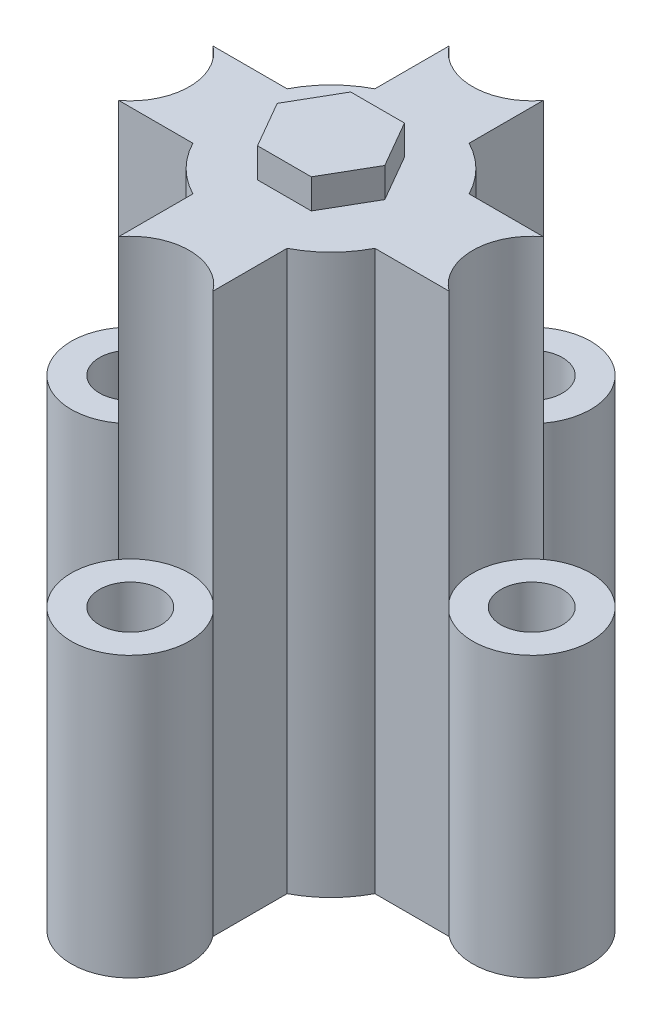
SolidWorks part; units mm, degrees
ref_plane "Front Plane" through (0, 0, 0) normal (0, 0, 1) x (1, 0, 0)
ref_plane "Top Plane" through (0, 0, 0) normal (0, 1, 0) x (1, 0, 0)
ref_plane "Right Plane" through (0, 0, 0) normal (1, 0, 0) x (0, 0, -1)
sketch "Sketch1" plane through (0, 0, 0) normal (0, 1, 0) x (1, 0, 0)
  line L1 (17.7275, 5.0583) -> (9.768, 5.0583)
  line L2 (17.7275, -5.0583) -> (9.768, -5.0583)
  line L3 (5.0583, -17.7275) -> (5.0583, -9.768)
  line L4 (-5.0583, -17.7275) -> (-5.0583, -9.768)
  line L5 (-17.7275, -5.0583) -> (-9.768, -5.0583)
  line L6 (-17.7275, 5.0583) -> (-9.768, 5.0583)
  line L7 (-5.0583, 17.7275) -> (-5.0583, 9.768)
  line L8 (5.0583, 17.7275) -> (5.0583, 9.768)
  circle A0 centre (0, 0) radius 11
  circle A4 centre (21.548, 0) radius 6.339
  circle A6 centre (0, -21.548) radius 6.339
  circle A8 centre (-21.548, 0) radius 6.339
  circle A10 centre (0, 21.548) radius 6.339
  circle A12 centre (21.548, 0) radius 3.302
  circle A13 centre (0, -21.548) radius 3.302
  circle A14 centre (-21.548, 0) radius 3.302
  circle A15 centre (0, 21.548) radius 3.302
  point P4 (13.7477, -5.0583)
  point P35 (0, 0)
  point P38 (0, 0)
  dimension "D1" = 21.548
  dimension "D2" = 12.678
  dimension "D3" = 6.604
  dimension "D5" = 22
  dimension "D4" = 7.9595
  dimension "D6" = 4
  dimension "D8" = 10.1166
  dimension "D9" = 7.9595
  dimension "D7" = 4
extrude "Boss-Extrude1" add sketch "Sketch1" along normal blind 60 contours A10 L7 A0 L8 | A8 L5 A0 L6 | A0 | A4 L1 A0 L2 | A6 L3 A0 L4 region at (13.3193, 0, 0) region at (0, 0, 0) region at (0, 0, -13.3193) region at (0, 0, 13.3193) region at (-13.3193, 0, 0)
extrude "Boss-Extrude2" add sketch "Sketch1<3>" along normal blind 30 contours A8 | A6 | A4 | A10 region at (24.2934, 0, -5.5141) region at (0, 0, -15.3883) region at (5.8403, 0, 19.5902) region at (-16.0339, 0, -2.7454)
sketch "Sketch1<3>" plane through (0, 0, 0) normal (0, 1, 0) x (1, 0, 0) same geometry as "Sketch1"
sketch "Sketch2" plane through (0, 60, 0) normal (0, 1, 0) x (1, 0, 0)
  line L1 (5.7735, 0) -> (2.8868, 5)
  line L2 (2.8868, 5) -> (-2.8868, 5)
  line L3 (-2.8868, 5) -> (-5.7735, 0)
  line L4 (-5.7735, 0) -> (-2.8868, -5)
  line L5 (-2.8868, -5) -> (2.8868, -5)
  line L6 (2.8868, -5) -> (5.7735, 0)
  circle A0 centre (0, 0) radius 5 construction
extrude "Boss-Extrude3" add sketch "Sketch2" along normal blind 3.175
